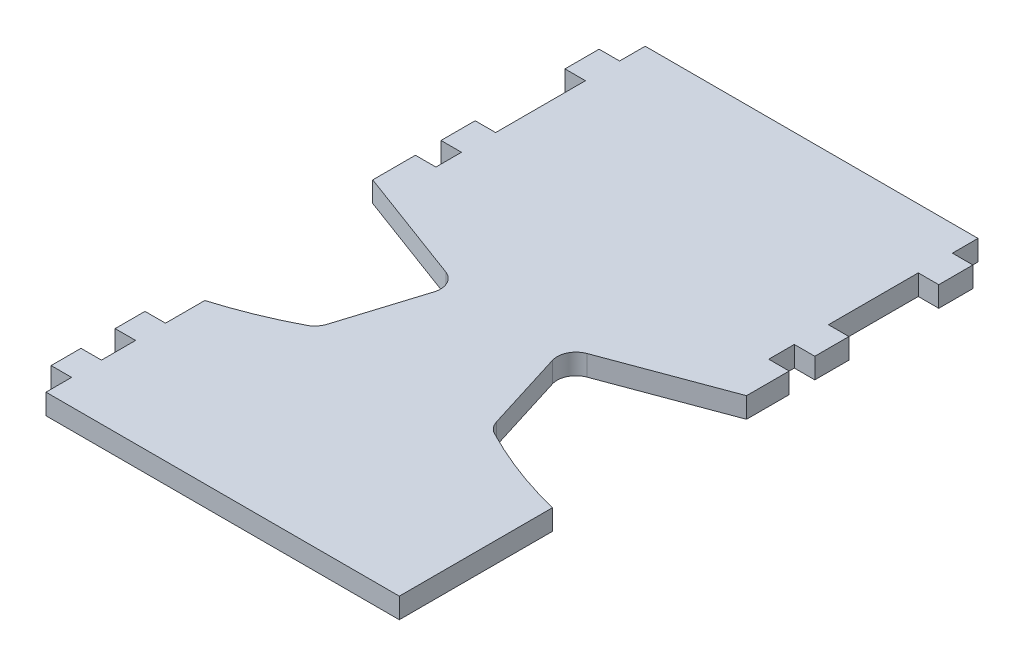
SolidWorks part; units mm, degrees
ref_plane "Front" through (0, 0, 0) normal (0, 0, 1) x (1, 0, 0)
ref_plane "Top" through (0, 0, 0) normal (0, 1, 0) x (1, 0, 0)
ref_plane "Right" through (0, 0, 0) normal (1, 0, 0) x (0, 0, -1)
ref_axis "side-side" through (80.9, 0, 0) along (-1, 0, 0)
ref_axis "up-down" through (0, 50, 0) along (0, -1, 0)
ref_axis "front-back" through (0, 0, -80.9) along (0, 0, 1)
sketch "Sketch1" plane through (0, 0, 0) normal (0, 1, 0) x (1, 0, 0)
  line L0 (0, 45.72) -> (0, 82.7528) construction
  line L1 (-49.53, 45.72) -> (49.53, 45.72)
  line L2 (-55.626, 38.1) -> (-55.626, 27.94)
  line L3 (-49.53, -132.6173) -> (55.626, -132.6173)
  line L4 (55.626, 38.1) -> (55.626, 27.94)
  line L8 (-17.632, -49.0369) -> (-25.1877, -73.287)
  line L9 (-21.0198, -42.1368) -> (-55.626, -29.2719)
  line L10 (-55.626, -97.0573) -> (-55.626, -105.9473)
  line L11 (55.626, -29.2719) -> (21.0198, -42.1368)
  line L12 (17.632, -49.0369) -> (25.1877, -73.287)
  line L13 (55.626, -87.0224) -> (55.626, -132.6173)
  line L14 (55.626, -16.5719) -> (55.626, -29.2719)
  line L15 (-49.53, 38.1) -> (-55.626, 38.1)
  line L16 (-49.53, 38.1) -> (-49.53, 45.72)
  line L17 (-55.626, -16.5719) -> (-55.626, -29.2719)
  line L19 (-49.53, -8.9519) -> (-55.626, -8.9519)
  line L20 (-49.53, -8.9519) -> (-49.53, -16.5719)
  line L21 (-49.53, -16.5719) -> (-55.626, -16.5719)
  line L24 (-49.53, -116.1073) -> (-55.626, -116.1073) construction
  line L25 (55.626, 38.1) -> (49.53, 38.1)
  line L26 (49.53, 45.72) -> (49.53, 38.1)
  line L27 (55.626, -16.5719) -> (49.53, -16.5719)
  line L29 (55.626, -8.9519) -> (49.53, -8.9519)
  line L30 (49.53, -16.5719) -> (49.53, -8.9519)
  line L32 (-49.53, -85.3598) -> (-49.53, -97.0573)
  line L33 (-55.626, -97.0573) -> (-49.53, -97.0573)
  line L36 (-49.53, -132.6173) -> (-49.53, -124.9973)
  line L37 (-55.626, -124.9973) -> (-49.53, -124.9973)
  line L38 (-49.53, -105.9473) -> (-49.53, -116.1073) construction
  line L39 (-55.626, -105.9473) -> (-49.53, -105.9473) construction
  line L40 (-49.53, -116.1073) -> (-55.626, -116.1073)
  line L41 (-49.53, -105.9473) -> (-49.53, -116.1073)
  line L42 (-55.626, -105.9473) -> (-49.53, -105.9473)
  line L43 (-49.53, 1.2081) -> (-55.626, 1.2081) construction
  line L44 (-55.626, 27.94) -> (-49.53, 27.94) construction
  line L45 (-49.53, 27.94) -> (-49.53, 1.2081) construction
  line L46 (-49.53, 1.2081) -> (-55.626, 1.2081)
  line L47 (-55.626, 27.94) -> (-49.53, 27.94)
  line L48 (-49.53, 27.94) -> (-49.53, 1.2081)
  line L49 (-55.626, 1.2081) -> (-55.626, -8.9519)
  line L50 (-55.626, -116.1073) -> (-55.626, -124.9973)
  line L51 (55.626, 1.2081) -> (49.53, 1.2081) construction
  line L52 (49.53, 1.2081) -> (49.53, 27.94) construction
  line L53 (49.53, 27.94) -> (55.626, 27.94) construction
  line L54 (55.626, 1.2081) -> (49.53, 1.2081)
  line L55 (49.53, 1.2081) -> (49.53, 27.94)
  line L56 (49.53, 27.94) -> (55.626, 27.94)
  line L57 (55.626, 1.2081) -> (55.626, -8.9519)
  arc A1 (-17.632, -49.0369) -> (-21.0198, -42.1368) centre (-22.967, -47.3746) ccw
  arc A2 (-27.9391, -76.5796) -> (-25.1877, -73.287) centre (-30.5228, -71.6248) ccw
  arc A3 (-27.9391, -76.5796) -> (-49.53, -85.3598) centre (-85.09, 33.02) cw
  arc A4 (21.0198, -42.1368) -> (17.632, -49.0369) centre (22.967, -47.3746) ccw
  arc A5 (25.1877, -73.287) -> (27.9391, -76.5796) centre (30.5228, -71.6248) ccw
  arc A6 (27.9391, -76.5796) -> (55.626, -87.0224) centre (85.09, 33.02) ccw
extrude "Boss-Extrude1" add sketch "Sketch1" along normal mid plane 6.096
